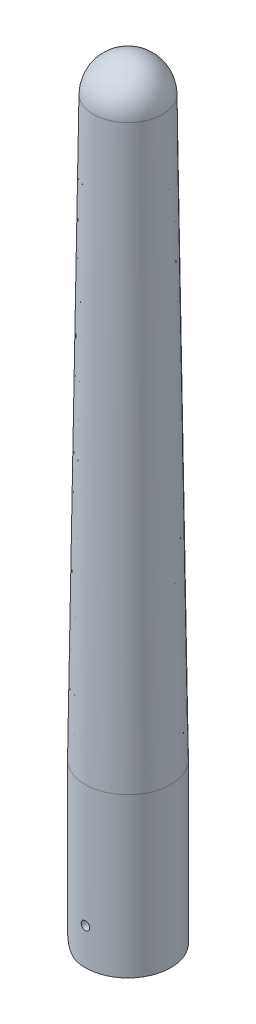
SolidWorks part; units mm, degrees
ref_plane "Front Plane" through (0, 0, 0) normal (0, 0, 1) x (1, 0, 0)
ref_plane "Top Plane" through (0, 0, 0) normal (0, 1, 0) x (1, 0, 0)
ref_plane "Right Plane" through (0, 0, 0) normal (1, 0, 0) x (0, 0, -1)
sketch "Sketch2" plane through (0, 0, 0) normal (0, 0, 1) x (1, 0, 0)
  line L0 (0, 0) -> (0, 105.1939) construction
  line L1 (0, 0) -> (5, 0)
  line L2 (5, 0) -> (5, 19.05)
  line L3 (5, 19.05) -> (4.0564, 86.424)
  line L4 (0, 90.424) -> (0, 0)
  arc A0 (4.0564, 86.424) -> (0, 90.424) centre (0, 86.3672) ccw
  dimension "D1" = 19.05
  dimension "D2" = 10
  dimension "D3" = 90.424
  dimension "D4" = 4
revolve "Revolve1" add sketch "Sketch2" angle 360 about L0
sketch "Sketch6" plane through (0, 0, 0) normal (0, 0, 1) x (1, 0, 0)
  line L1 (-4, 3.5) -> (-4, 7)
  line L3 (-5, 19.05) -> (-5, 0) construction
  line L4 (-5, 0) -> (-5, 8)
  line L5 (-4, 7) -> (-5, 8)
  line L6 (-5, 0) -> (5, 0) construction
  line L7 (-1, 0.5) -> (5, 0.5)
  line L8 (5, 0) -> (5, 19.05) construction
  line L9 (5, 0.5) -> (5, 0)
  line L10 (5, 0) -> (-5, 0)
  arc A0 (-1, 0.5) -> (-4, 3.5) centre (-1, 3.5) cw
  dimension "D1" = 45
  dimension "D2" = 1
  dimension "D3" = 4
  dimension "D4" = 8
  dimension "D5" = 0.5
extrude "Cut-Extrude1" cut sketch "Sketch6" against normal through all both and the other way through all
sketch "Sketch7" plane through (0, 0, 0) normal (0, 0, 1) x (1, 0, 0)
  circle A0 centre (0, 4.7625) radius 0.5
  point P2 (0, 0)
  dimension "D1" = 1
  dimension "D2" = 4.7625
extrude "Cut-Extrude2" cut sketch "Sketch7" against normal through all both and the other way through all
sketch "Sketch8" plane through (0, 0.5, 0) normal (0, -1, 0) x (1, 0, 0)
  line L0 (0, 3) -> (-5, 3)
  line L1 (-5, 3) -> (-5, -3)
  line L2 (-5, -3) -> (0, -3)
  arc A0 (0, -3) -> (0, 3) centre (0, 0) ccw
  arc A1 (-4, 3) -> (-4, -3) centre (0, 0) ccw construction
  point P9 (0, 0)
  point P11 (0, 0)
extrude "Cut-Extrude3" cut sketch "Sketch8" against normal up to vertex (6.5 mm away) up to point (-4, 7, 3)
